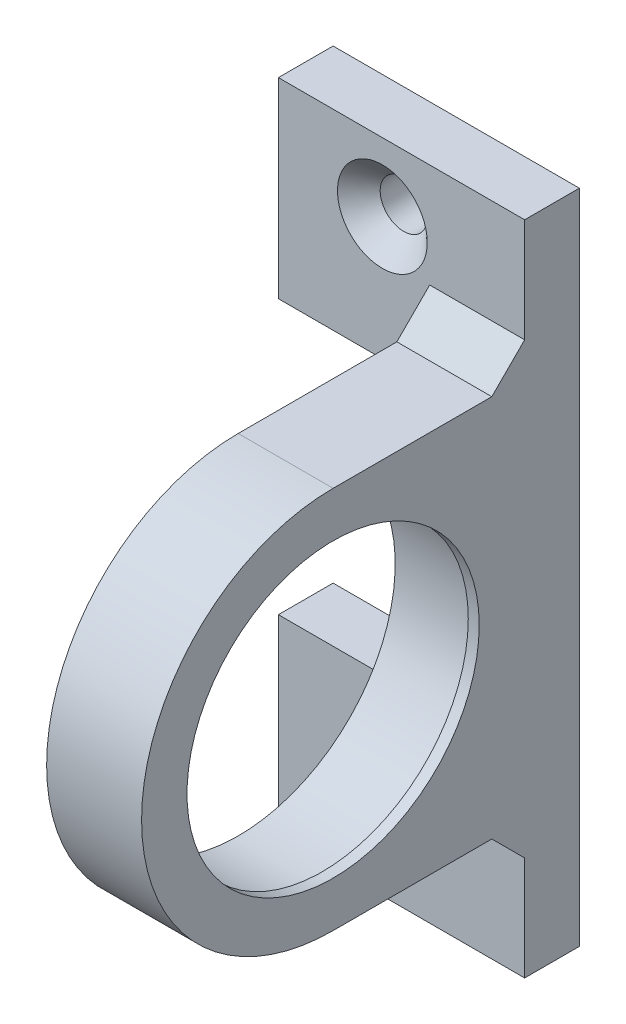
SolidWorks part; units mm, degrees
ref_plane "前视基准面" through (0, 0, 0) normal (0, 0, 1) x (1, 0, 0)
ref_plane "上视基准面" through (0, 0, 0) normal (0, 1, 0) x (1, 0, 0)
ref_plane "右视基准面" through (0, 0, 0) normal (1, 0, 0) x (0, 0, -1)
sketch "草图2" plane through (0, 0, 0) normal (0, 0, 1) x (1, 0, 0)
  line L0 (-14.7736, 24.3382) -> (-14.7736, -35.6618)
  line L1 (-14.7736, -35.6618) -> (30.2264, -35.6618)
  line L2 (7.7264, -35.6618) -> (7.7264, -18.1618)
  line L3 (21.55, -18.1618) -> (-6.0971, -18.1618)
  line L4 (-6.0971, -18.1618) -> (-6.0971, 6.8382)
  line L5 (-6.0971, 6.8382) -> (21.55, 6.8382)
  line L6 (7.7264, 6.8382) -> (7.7264, 24.3382)
  line L7 (30.2264, 24.3382) -> (-14.7736, 24.3382)
  line L8 (7.7264, 28.8603) -> (7.7264, -39.8897) construction
  line L9 (21.55, -18.1618) -> (21.55, 6.8382)
  line L10 (30.2264, 24.3382) -> (30.2264, -35.6618)
  line L11 (-18.1559, -5.6618) -> (33.2411, -5.6618) construction
  line L12 (44.0218, -5.6618) -> (44.0218, 26.2521) construction
  point P16 (-6.0971, -5.6618)
  point P17 (-14.7736, -5.6618)
  dimension "D1" = 45
  dimension "D2" = 25
  dimension "D3" = 60
extrude "凸台-拉伸2" add sketch "草图2" along normal blind 5 contours L6 L7 L0 L1 L2 L3 L4 L5 | L10 L7 L6 L5 L9 L3 L2 L1 region at (-3.5236, 23.6974, 0) region at (18.9764, 23.6974, 0)
sketch "草图4" plane through (0, 0, 5) normal (0, 0, 1) x (1, 0, 0)
  line L0 (-18.165, -5.6618) -> (33.9165, -5.6618) construction
  line L1 (-14.7736, 24.3382) -> (-14.7736, -35.6618) construction
  line L2 (-14.7736, -23.1618) -> (-6.0971, -23.1618)
  line L3 (-14.7736, -23.1618) -> (-14.7736, 11.8382)
  line L4 (-14.7736, 11.8382) -> (-6.0971, 11.8382)
  line L5 (-6.0971, -23.1618) -> (-6.0971, 11.8382)
  line L6 (-6.0971, -18.1618) -> (-6.0971, 6.8382) construction
  line L7 (7.7264, -39.813) -> (7.7264, 28.1228) construction
  line L8 (30.2264, 11.8382) -> (21.55, 11.8382)
  line L9 (21.55, -23.1618) -> (21.55, 11.8382)
  line L10 (30.2264, -23.1618) -> (21.55, -23.1618)
  line L11 (30.2264, -23.1618) -> (30.2264, 11.8382)
  point P17 (-14.7736, -5.6618)
  dimension "D1" = 35
extrude "凸台-拉伸15" add sketch "草图4" along normal blind 35
sketch "草图5" plane through (-14.7736, 0, 0) normal (-1, 0, 0) x (0, 0, 1)
  line L0 (0, -5.6618) -> (40, -5.6618)
  line L1 (0, 24.3382) -> (0, -35.6618) construction
  line L2 (40, 11.8382) -> (40, -23.1618) construction
  line L3 (22.5, 11.8382) -> (40, 11.8382)
  line L4 (40, 11.8382) -> (40, -23.1618)
  line L5 (40, -23.1618) -> (22.5, -23.1618)
  circle A0 centre (22.5, -5.6618) radius 17.5
  line M5 (5, -23.1618) -> (40, -23.1618)
  line M6 (40, -23.1618) -> (40, 11.8382)
  line M7 (40, 11.8382) -> (5, 11.8382)
  dimension "D1" = 35
extrude "切除-拉伸1" cut sketch "草图5" against normal blind 45 contours A0 M5 M6 | A0 M6 M7 region at (-14.7736, 7.9293, 36.0911) region at (-14.7736, -19.2528, 36.0911)
sketch "草图6" plane through (-14.7736, 0, 0) normal (-1, 0, 0) x (0, 0, 1)
  circle A0 centre (22.5, -5.6618) radius 14.35
  dimension "D1" = 28.7
extrude "切除-拉伸2" cut sketch "草图6" against normal blind 45
fillet "圆角1" radius 5 4 edges at (-6.0971, 6.8382, 2.5) (21.55, 6.8382, 2.5) (-6.0971, -18.1618, 2.5) (21.55, -18.1618, 2.5)
sketch "草图7" plane through (-6.0971, 0, 0) normal (1, 0, 0) x (0, 0, -1)
  circle A0 centre (-22.5, -5.6618) radius 15
  circle A1 centre (-22.5, -5.6618) radius 13
extrude "凸台-拉伸16" add sketch "草图7" against normal blind 1
sketch "草图8" plane through (21.55, 0, 0) normal (-1, 0, 0) x (0, 0, 1)
  circle A0 centre (22.5, -5.6618) radius 15
  circle A1 centre (22.5, -5.6618) radius 10
sketch "草图9" plane through (0, 0, 5) normal (0, 0, 1) x (1, 0, 0)
  line L0 (7.7264, 24.3382) -> (7.7264, -35.6618)
  line L13 (30.2264, 24.3382) -> (-14.7736, 24.3382) construction
  line L14 (-14.7736, -35.6618) -> (30.2264, -35.6618) construction
sketch "草图11" plane through (0, 0, 5) normal (0, 0, 1) x (1, 0, 0)
  line L0 (-14.7736, 18.0882) -> (30.2264, 18.0882)
  line L1 (-14.7736, 24.3382) -> (-14.7736, 11.8382) construction
  line L2 (30.2264, 24.3382) -> (30.2264, 11.8382) construction
  line L3 (7.7264, 24.3382) -> (7.7264, -35.6618) construction
  line L4 (30.2264, 24.3382) -> (-14.7736, 24.3382) construction
  line L5 (-14.7736, -35.6618) -> (30.2264, -35.6618) construction
  line L6 (7.7264, -5.6618) -> (45.6912, -5.6618) construction
  line L10 (-14.7736, -29.4118) -> (30.2264, -29.4118)
  line L11 (-14.7736, -23.1618) -> (-14.7736, -35.6618) construction
  point P4 (-1.7736, 18.0882)
  point P16 (-1.7736, -29.4118)
  point P18 (17.2264, -29.4118)
  point P25 (17.2264, 18.0882)
  dimension "D1" = 13
split "分割1" trim tools "草图9" bodies to split 111 resulting bodies 117 118
delete or keep bodies "实体-删除/保留 2" type delete bodies bodies 117
hole_wizard "打孔尺寸(%根据)内六角花形半沉头螺钉的类型1" positions "3D草图2" profile "草图13" countersink size "M6" standard "GB"
sketch3d "3D草图2"
  point P0 (17.2264, 18.0882, 5)
  point P3 (17.2264, -29.4118, 5)
sketch "草图13" plane through (17.2264, 18.0882, 5) normal (1, 0, 0) x (0, -1, 0)
  line L0 (0, 0) -> (0, 6.2919)
  line L1 (0, 6.2919) -> (2.15, 5)
  line L2 (2.15, 5) -> (2.15, 1.95)
  line L3 (2.15, 1.95) -> (4.1, 0)
  line L5 (4.1, 0) -> (0, 0)
  line L6 (-2.15, 1.95) -> (-4.1, 0) construction
  line L10 (0, 6.2919) -> (-2.15, 5) construction
  line L11 (0, -6.35) -> (0, 107.95) construction
  dimension "孔直径" = 4.3
  dimension "孔深度" = 5
  dimension "近端锥形沉头孔直径" = 8.2
  dimension "近端锥形沉头孔角度" = 90
  dimension "导头角度" = 118
ref_plane "基准面1" through (30.2264, 0, 0) normal (1, 0, 0) x (0, 0, -1)
sketch "草图14" plane through (30.2264, 0, 0) normal (1, 0, 0) x (0, 0, -1)
  circle A1 centre (-22.5, -5.6618) radius 14.35 construction
  circle A3 centre (-22.5, -5.6618) radius 14.35
extrude "拉伸-薄壁1" add sketch "草图14" against normal blind 1 thin thin type one direction reverse wall 1
chamfer "倒角1" distance 3 angle 45 2 edges at (25.8882, -23.1618, 5) (25.8882, 11.8382, 5)
